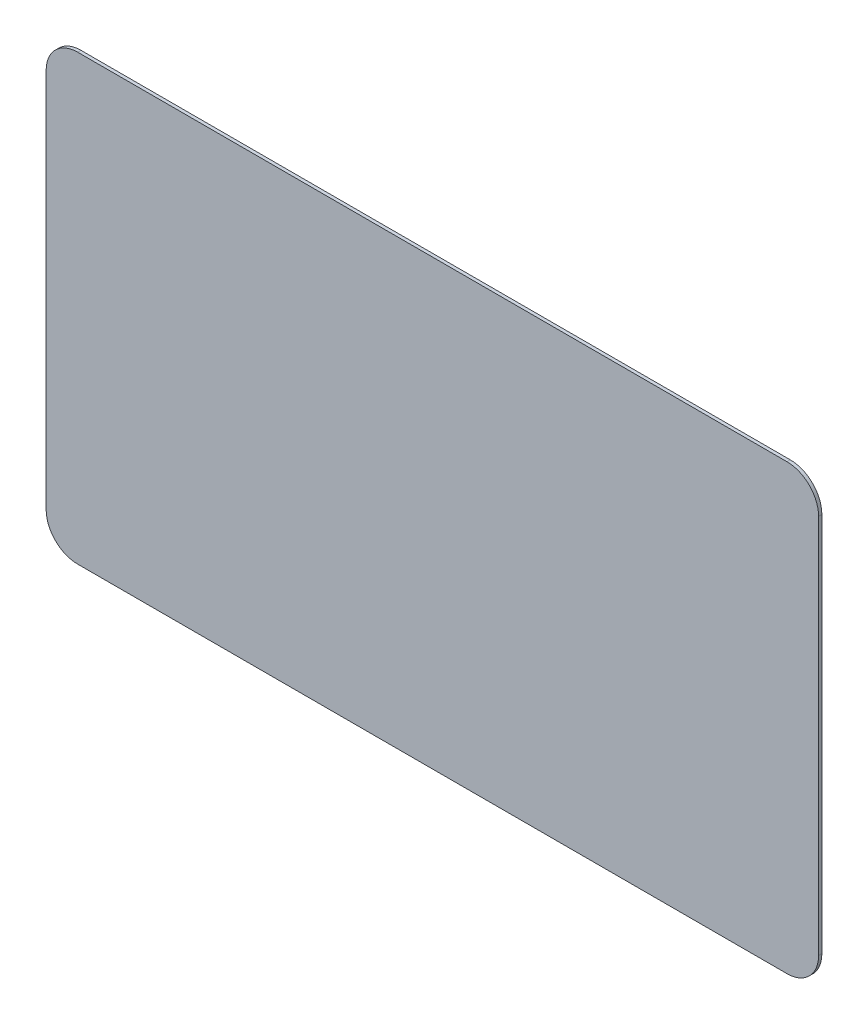
SolidWorks part; units mm, degrees
ref_plane "Plan de face" through (0, 0, 0) normal (0, 0, 1) x (1, 0, 0)
ref_plane "Plan de dessus" through (0, 0, 0) normal (0, 1, 0) x (1, 0, 0)
ref_plane "Plan de droite" through (0, 0, 0) normal (1, 0, 0) x (0, 0, -1)
sketch "Esquisse1" plane through (0, 0, 0) normal (0, 0, 1) x (1, 0, 0)
  line L1 (96.48, -55.38) -> (-96.48, -55.38)
  line L2 (96.48, -55.38) -> (96.48, 55.38)
  line L3 (96.48, 55.38) -> (-96.48, 55.38)
  line L4 (-96.48, -55.38) -> (-96.48, 55.38)
  line L5 (96.48, -55.38) -> (-96.48, 55.38) construction
  line L6 (96.48, 55.38) -> (-96.48, -55.38) construction
  point P0 (0, 0)
  dimension "D1" = 192.96
  dimension "D2" = 110.76
extrude "c_vitre" add sketch "Esquisse1" along normal blind 0.82
fillet "Congé1" radius 7.88 4 edges at (-96.48, 55.38, 0.41) (-96.48, -55.38, 0.41) (96.48, -55.38, 0.41) (96.48, 55.38, 0.41)
sketch "Esquisse2" plane through (0, 0, 0) normal (0, 0, -1) x (-1, 0, 0)
  line L0 (-88.6, 55.38) -> (88.6, 55.38) construction
  line L1 (91.5, -49.06) -> (-79.88, -49.06)
  line L2 (91.5, -49.06) -> (91.5, 47.9)
  line L3 (91.5, 47.9) -> (-79.88, 47.9)
  line L4 (-79.88, -49.06) -> (-79.88, 47.9)
  line L5 (91.5, -49.06) -> (-79.88, 47.9) construction
  line L6 (91.5, 47.9) -> (-79.88, -49.06) construction
  line L7 (88.6, -55.38) -> (-88.6, -55.38) construction
  line L8 (96.48, 47.5) -> (96.48, -47.5) construction
  line L9 (-96.48, -47.5) -> (-96.48, 47.5) construction
  point P0 (5.81, -0.58)
  dimension "D1" = 7.48
  dimension "D2" = 6.32
  dimension "D3" = 4.98
  dimension "D4" = 16.6
extrude "c_touch" add sketch "Esquisse2" along normal blind 0.8
sketch "Esquisse3" plane through (0, 0, -0.8) normal (0, 0, -1) x (-1, 0, 0)
  line L0 (-88.6, 55.38) -> (88.6, 55.38) construction
  line L1 (-84.59, 48.75) -> (81.61, 48.75)
  line L2 (-84.59, 48.75) -> (-84.59, -51.85)
  line L3 (-84.59, -51.85) -> (81.61, -51.85)
  line L4 (81.61, 48.75) -> (81.61, -51.85)
  line L5 (-84.59, 48.75) -> (81.61, -51.85) construction
  line L6 (-84.59, -51.85) -> (81.61, 48.75) construction
  line L7 (-96.48, -47.5) -> (-96.48, 47.5) construction
  point P0 (-1.49, -1.55)
  dimension "D1" = 100.6
  dimension "D2" = 166.2
  dimension "D3" = 6.63
  dimension "D4" = 11.89
extrude "Boss.-Extru.3" add sketch "Esquisse3" along normal blind 4.58
sketch "Esquisse4" plane through (0, 0, -5.38) normal (0, 0, -1) x (-1, 0, 0)
  line L0 (-84.59, 48.75) -> (-84.59, -51.85) construction
  line L1 (-57.09, 29.8) -> (-72.09, 29.8)
  line L2 (-57.09, 29.8) -> (-57.09, 37.8)
  line L3 (-57.09, 37.8) -> (-72.09, 37.8)
  line L4 (-72.09, 29.8) -> (-72.09, 37.8)
  line L5 (-57.09, 29.8) -> (-72.09, 37.8) construction
  line L6 (-57.09, 37.8) -> (-72.09, 29.8) construction
  line L7 (-57.09, -35.8128) -> (-72.09, -35.8128)
  line L8 (-57.09, -35.8128) -> (-57.09, -27.8128)
  line L9 (-57.09, -27.8128) -> (-72.09, -27.8128)
  line L10 (-72.09, -35.8128) -> (-72.09, -27.8128)
  line L11 (-57.09, -35.8128) -> (-72.09, -27.8128) construction
  line L12 (-57.09, -27.8128) -> (-72.09, -35.8128) construction
  line L13 (69.11, -35.8128) -> (54.11, -35.8128)
  line L14 (69.11, -35.8128) -> (69.11, -27.8128)
  line L15 (69.11, -27.8128) -> (54.11, -27.8128)
  line L16 (54.11, -35.8128) -> (54.11, -27.8128)
  line L17 (69.11, -35.8128) -> (54.11, -27.8128) construction
  line L18 (69.11, -27.8128) -> (54.11, -35.8128) construction
  line L19 (69.11, 37.8372) -> (54.11, 37.8372)
  line L20 (69.11, 37.8372) -> (69.11, 29.8372)
  line L21 (69.11, 29.8372) -> (54.11, 29.8372)
  line L22 (54.11, 37.8372) -> (54.11, 29.8372)
  line L23 (69.11, 37.8372) -> (54.11, 29.8372) construction
  line L24 (69.11, 29.8372) -> (54.11, 37.8372) construction
  line L25 (-39.49, 35.45) -> (-31.49, 35.45)
  line L26 (-39.49, 35.45) -> (-39.49, 20.45)
  line L27 (-39.49, 20.45) -> (-31.49, 20.45)
  line L28 (-31.49, 35.45) -> (-31.49, 20.45)
  line L29 (-39.49, 35.45) -> (-31.49, 20.45) construction
  line L30 (-39.49, 20.45) -> (-31.49, 35.45) construction
  line L31 (-39.49, -13.55) -> (-31.49, -13.55)
  line L32 (-39.49, -13.55) -> (-39.49, -28.55)
  line L33 (-39.49, -28.55) -> (-31.49, -28.55)
  line L34 (-31.49, -13.55) -> (-31.49, -28.55)
  line L35 (-39.49, -13.55) -> (-31.49, -28.55) construction
  line L36 (-39.49, -28.55) -> (-31.49, -13.55) construction
  line L37 (18.51, -13.55) -> (26.51, -13.55)
  line L38 (18.51, -13.55) -> (18.51, -28.55)
  line L39 (18.51, -28.55) -> (26.51, -28.55)
  line L40 (26.51, -13.55) -> (26.51, -28.55)
  line L41 (18.51, -13.55) -> (26.51, -28.55) construction
  line L42 (18.51, -28.55) -> (26.51, -13.55) construction
  line L43 (18.51, 35.45) -> (26.51, 35.45)
  line L44 (18.51, 35.45) -> (18.51, 20.45)
  line L45 (18.51, 20.45) -> (26.51, 20.45)
  line L46 (26.51, 35.45) -> (26.51, 20.45)
  line L47 (18.51, 35.45) -> (26.51, 20.45) construction
  line L48 (18.51, 20.45) -> (26.51, 35.45) construction
  line L49 (-88.6, 55.38) -> (88.6, 55.38) construction
  line L50 (-83.94, 63.8022) -> (-83.94, -60.8161) construction
  line L51 (-96.48, -47.5) -> (-96.48, 47.5) construction
  line L52 (81.61, 48.75) -> (-84.59, 48.75) construction
  circle A0 centre (-64.59, 33.8) radius 1.5
  circle A1 centre (-64.59, -31.8128) radius 1.5
  circle A2 centre (61.61, -31.8128) radius 1.5
  circle A3 centre (61.61, 33.8372) radius 1.5
  circle A4 centre (-35.49, 27.95) radius 1.25
  circle A5 centre (-35.49, -21.05) radius 1.25
  circle A6 centre (22.51, -21.05) radius 1.25
  circle A7 centre (22.51, 27.95) radius 1.25
  point P0 (-64.59, 33.8)
  point P5 (-64.59, -31.8128)
  point P10 (61.61, -31.8128)
  point P15 (61.61, 33.8372)
  point P20 (-35.49, 27.95)
  point P25 (-35.49, -21.05)
  point P30 (22.51, -21.05)
  point P35 (22.51, 27.95)
  dimension "D3" = 3
  dimension "D4" = 3
  dimension "D5" = 3
  dimension "D6" = 3
  dimension "D16" = 2.5
  dimension "D17" = 2.5
  dimension "D18" = 2.5
  dimension "D19" = 2.5
  dimension "D1" = 15
  dimension "D2" = 8
  dimension "D7" = 20
  dimension "D8" = 126.2
  dimension "D9" = 21.58
  dimension "D10" = 65.65
  dimension "D11" = 12.54
  dimension "D12" = 48.45
  dimension "D13" = 58
  dimension "D14" = 20.8
  dimension "D15" = 49
extrude "Boss.-Extru.4" add sketch "Esquisse4" along normal blind 2.5
chamfer "Chanfrein1" distance 2.5 distance2 4.5 16 edges at (-69.11, -31.8128, -7.88) (-54.11, -31.8128, -7.88) (-22.51, -28.55, -7.88) (-22.51, -13.55, -7.88) (-69.11, 33.8372, -7.88) (-54.11, 33.8372, -7.88) (-22.51, 20.45, -7.88) (-22.51, 35.45, -7.88) (35.49, 35.45, -7.88) (57.09, 33.8, -7.88) (72.09, 33.8, -7.88) (35.49, 20.45, -7.88) (35.49, -13.55, -7.88) (35.49, -28.55, -7.88) (57.09, -31.8128, -7.88) (72.09, -31.8128, -7.88) first distance on face at (-69.11, -31.8128, -6.63) first distance on face at (-54.11, -31.8128, -6.63) first distance on face at (-22.51, -28.55, -6.63) first distance on face at (-22.51, -13.55, -6.63) first distance on face at (-69.11, 33.8372, -6.63) first distance on face at (-54.11, 33.8372, -6.63) first distance on face at (-22.51, 20.45, -6.63) first distance on face at (-22.51, 35.45, -6.63) first distance on face at (35.49, 35.45, -6.63) first distance on face at (57.09, 33.8, -6.63) first distance on face at (72.09, 33.8, -6.63) first distance on face at (35.49, 20.45, -6.63) first distance on face at (35.49, -13.55, -6.63) first distance on face at (35.49, -28.55, -6.63) first distance on face at (57.09, -31.8128, -6.63) first distance on face at (72.09, -31.8128, -6.63)
sketch "Esquisse5" plane through (0, 0, -5.38) normal (0, 0, -1) x (-1, 0, 0)
  line L0 (-84.59, -1.55) -> (81.61, -1.55) construction
  line L1 (-50.49, 45.85) -> (47.51, 45.85)
  line L3 (-50.49, 42.85) -> (47.51, 42.85)
  line L5 (-50.49, 45.85) -> (47.51, 42.85) construction
  line L6 (-50.49, 42.85) -> (47.51, 45.85) construction
  line L7 (-84.59, 48.75) -> (-84.59, -51.85) construction
  line L8 (81.61, -51.85) -> (81.61, 48.75) construction
  line L9 (81.61, 48.75) -> (-84.59, 48.75) construction
  line L10 (-1.49, 48.75) -> (-1.49, -51.85) construction
  line L11 (-84.59, -51.85) -> (81.61, -51.85) construction
  line L13 (-30.49, -43.85) -> (27.51, -43.85)
  line L15 (-30.49, -46.85) -> (27.51, -46.85)
  line L17 (-30.49, -43.85) -> (27.51, -46.85) construction
  line L18 (-30.49, -46.85) -> (27.51, -43.85) construction
  arc A0 (-50.3982, 45.8472) -> (-50.3982, 42.8528) centre (-50.49, 44.35) ccw
  arc A1 (47.4182, 42.8528) -> (47.4182, 45.8472) centre (47.51, 44.35) ccw
  arc A2 (-30.3352, -43.858) -> (-30.3352, -46.842) centre (-30.49, -45.35) ccw
  arc A3 (27.3552, -46.842) -> (27.3552, -43.858) centre (27.51, -45.35) ccw
  point P0 (-1.49, 44.35)
  point P21 (-1.49, -45.35)
  dimension "D1" = 3
  dimension "D3" = 2.9
  dimension "D5" = 3
  dimension "D7" = 5
extrude "Boss.-Extru.5" add sketch "Esquisse5" along normal blind 0.5 contours L15 A3 L13 A2 | L3 A1 L1 A0 region at (1.49, 44.35, -5.38) region at (1.49, -45.35, -5.38)
fillet "Congé2" radius 0.5 8 edges at (1.49, 42.85, -5.88) (51.99, 44.35, -5.88) (1.49, 45.85, -5.88) (1.49, -46.85, -5.88) (31.99, -45.35, -5.88) (1.49, -43.85, -5.88) (-49.01, 44.35, -5.88) (-29.01, -45.35, -5.88)
sketch "Esquisse7" plane through (0, -35.8128, 0) normal (0, -1, 0) x (1, 0, 0)
  line L0 (58.7373, -5.38) -> (70.4427, -5.38)
  line L1 (84.59, -5.38) -> (-81.61, -5.38) construction
  line L2 (72.09, -5.38) -> (57.09, -5.38) construction
  line L3 (70.4427, -5.38) -> (67.3827, -7.08)
  line L4 (67.3827, -7.08) -> (61.7973, -7.08)
  line L5 (61.7973, -7.08) -> (58.7373, -5.38)
  line L6 (57.09, -5.38) -> (61.59, -7.88) construction
  line L7 (67.59, -7.88) -> (72.09, -5.38) construction
  line L8 (67.59, -7.88) -> (61.59, -7.88) construction
  line L9 (1.49, -5.38) -> (1.49, -22.4859) construction
  line L10 (-67.4627, -5.38) -> (-64.4027, -7.08)
  line L11 (-55.7573, -5.38) -> (-67.4627, -5.38)
  line L12 (-58.8173, -7.08) -> (-55.7573, -5.38)
  line L13 (-64.4027, -7.08) -> (-58.8173, -7.08)
  dimension "D1" = 0.8
  dimension "D2" = 0.8
  dimension "D3" = 0.8
extrude "Enlèv. mat.-Extru.1" cut sketch "Esquisse7" against normal through all
sketch "Esquisse8" plane through (39.49, 0, 0) normal (1, 0, 0) x (0, 0, -1)
  line L0 (5.38, -15.1973) -> (5.38, -26.9027)
  line L1 (5.38, -13.55) -> (5.38, -28.55) construction
  line L2 (5.38, -26.9027) -> (7.08, -23.8427)
  line L3 (7.08, -23.8427) -> (7.08, -18.2573)
  line L4 (7.08, -18.2573) -> (5.38, -15.1973)
  line L5 (7.88, -18.05) -> (5.38, -13.55) construction
  line L6 (7.88, -18.05) -> (7.88, -24.05) construction
  line L7 (5.38, -28.55) -> (7.88, -24.05) construction
  dimension "D1" = 0.8
  dimension "D2" = 0.8
  dimension "D3" = 0.8
extrude "Enlèv. mat.-Extru.2" cut sketch "Esquisse8" against normal up to surface (66 mm away) up to face at (-26.51, -21.05, -6.63)
sketch "Esquisse9" plane through (39.49, 0, 0) normal (1, 0, 0) x (0, 0, -1)
  line L0 (5.38, 22.0973) -> (5.38, 33.8027)
  line L1 (5.38, 48.75) -> (5.38, -51.85) construction
  line L2 (5.38, 33.8027) -> (7.08, 30.7427)
  line L3 (7.08, 30.7427) -> (7.08, 25.1573)
  line L4 (7.08, 25.1573) -> (5.38, 22.0973)
  line L5 (7.88, 30.95) -> (5.38, 35.45) construction
  line L6 (7.88, 30.95) -> (7.88, 24.95) construction
  line L7 (5.38, 20.45) -> (7.88, 24.95) construction
  dimension "D1" = 0.8
  dimension "D2" = 0.8
  dimension "D3" = 0.8
extrude "Enlèv. mat.-Extru.3" cut sketch "Esquisse9" against normal up to surface (66 mm away) up to face at (-26.51, 27.95, -6.63)
